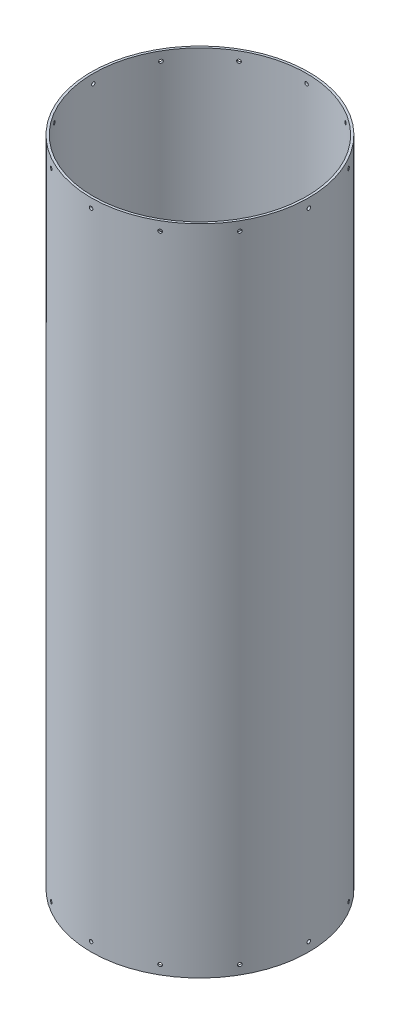
SolidWorks part; units mm, degrees
material "Hexcel AS4C (3000 Filaments)"
ref_plane "Front Plane" through (0, 0, 0) normal (0, 0, 1) x (1, 0, 0)
ref_plane "Top Plane" through (0, 0, 0) normal (0, 1, 0) x (1, 0, 0)
ref_plane "Right Plane" through (0, 0, 0) normal (1, 0, 0) x (0, 0, -1)
sketch "Sketch1" plane through (0, 0, 0) normal (0, 1, 0) x (1, 0, 0)
  circle A0 centre (0, 0) radius 152.4
  circle A1 centre (0, 0) radius 149.225
  dimension "D2" = 304.8
  dimension "D1" = 3.175
extrude "Boss-Extrude1" add sketch "Sketch1" along normal blind 914.4
ref_plane "Plane1" through (-152.4, 0, 0) normal (-1, 0, 0) x (0, 0, 1)
hole_wizard "#10 (0.1935) Diameter Hole1" positions "Sketch2" profile "Sketch3" hole size "#10" standard "ANSI Inch" end condition up to next
sketch "Sketch2" plane through (-152.4, 0, 0) normal (-1, 0, 0) x (0, 0, 1)
  line L0 (0, -167.64) -> (0, 167.64) construction
  line L1 (152.4, 914.4) -> (-152.4, 914.4) construction
  point P0 (0, 901.7)
  dimension "D1" = 12.7
sketch "Sketch3" plane through (-152.4, 901.7, 0) normal (0, 1, 0) x (0, 0, 1)
  line L0 (0, 0) -> (0, 356.2465)
  line L1 (0, 356.2465) -> (2.4574, 356.2465)
  line L2 (2.4574, 356.2465) -> (2.4574, 0)
  line L5 (2.4574, 0) -> (0, 0)
  line L11 (0, -6.35) -> (0, 107.95) construction
  dimension "Thru Hole Dia." = 4.9149
  dimension "Thru Hole Depth" = 356.2465
pattern_circular "CirPattern1" count 12 over 360 about axis through (0, 914.4, 0) along (0, 1, 0) of "#10 (0.1935) Diameter Hole1"
ref_plane "Plane2" through (0, 457.2, 0) normal (0, 1, 0) x (1, 0, 0)
mirror "Mirror1" about plane through (0, 457.2, 0) normal (0, 1, 0) of "CirPattern1"
